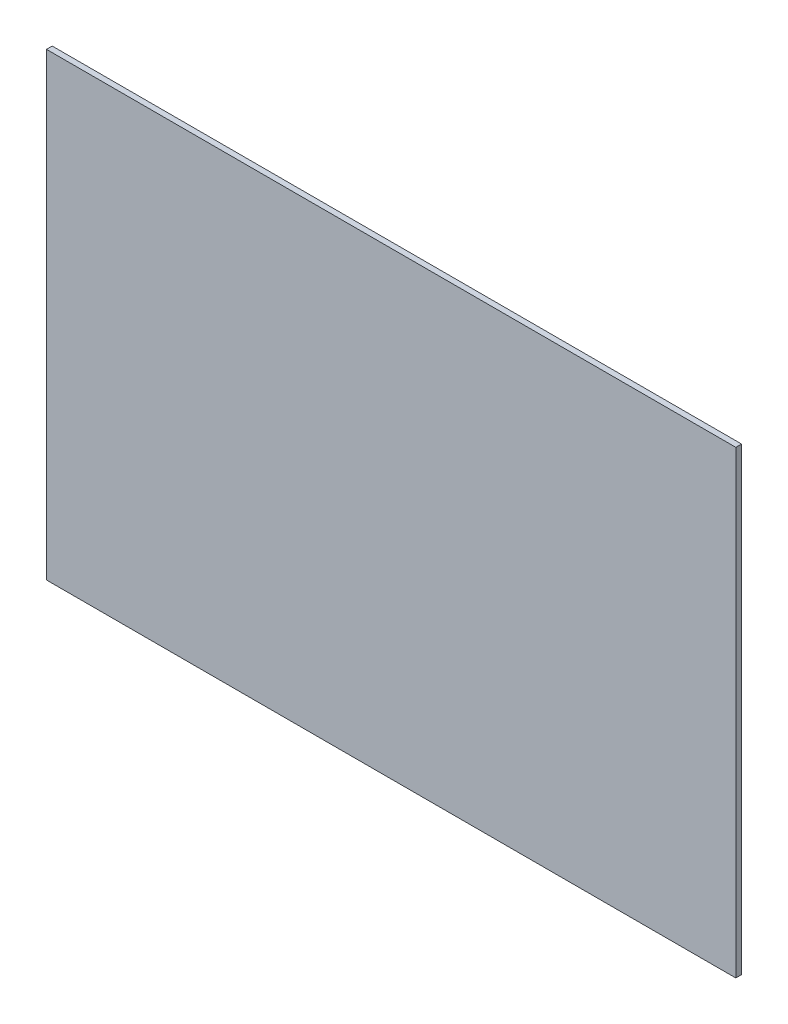
SolidWorks part; units mm, degrees
ref_plane "Front Plane" through (0, 0, 0) normal (0, 0, 1) x (1, 0, 0)
ref_plane "Top Plane" through (0, 0, 0) normal (0, 1, 0) x (1, 0, 0)
ref_plane "Right Plane" through (0, 0, 0) normal (1, 0, 0) x (0, 0, -1)
sketch "Sketch1" plane through (0, 0, 0) normal (0, 0, 1) x (1, 0, 0)
  line L1 (0, 0) -> (304.8, 0)
  line L2 (0, 0) -> (0, 203.2)
  line L3 (0, 203.2) -> (304.8, 203.2)
  line L4 (304.8, 0) -> (304.8, 203.2)
  dimension "D1" = 304.8
  dimension "D2" = 203.2
extrude "Boss-Extrude1" add sketch "Sketch1" along normal blind 2.54
